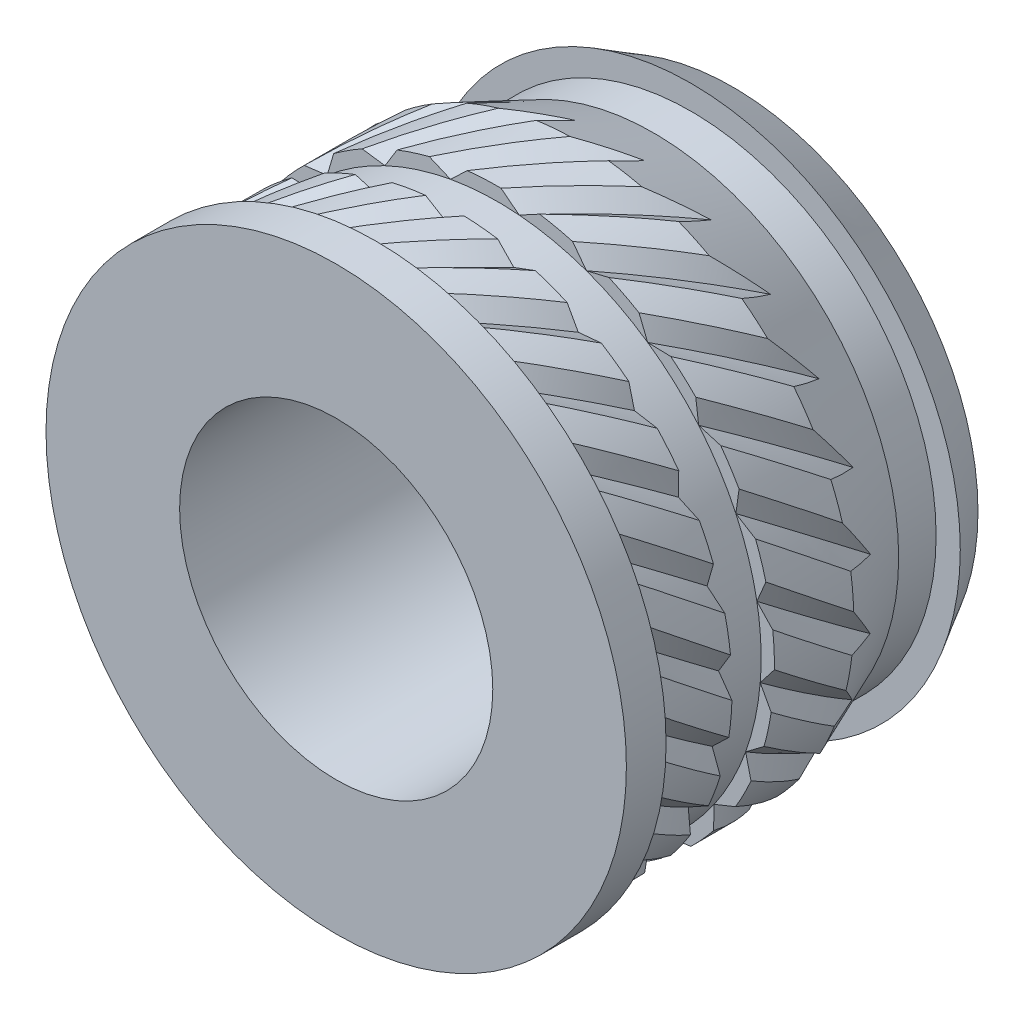
SolidWorks part; units mm, degrees
material "Brass"
ref_plane "Front Plane" through (0, 0, 0) normal (0, 0, 1) x (1, 0, 0)
ref_plane "Top Plane" through (0, 0, 0) normal (0, 1, 0) x (1, 0, 0)
ref_plane "Right Plane" through (0, 0, 0) normal (1, 0, 0) x (0, 0, -1)
sketch "Sketch1" plane through (0, 0, 0) normal (1, 0, 0) x (0, 0, -1)
  line L0 (-1.9, 0) -> (1.9, 0) construction
  line L1 (-1.9, 1.5) -> (-1.9, 2.78)
  line L2 (-1.9, 2.78) -> (-1.52, 2.78)
  line L3 (-1.52, 2.78) -> (-1.52, 2.6525)
  line L4 (-1.52, 2.6525) -> (-0.76, 2.6525)
  line L5 (-0.76, 2.6525) -> (-0.76, 2.525)
  line L6 (-0.76, 2.525) -> (-0.3545, 2.525)
  line L7 (-0.3545, 2.525) -> (-0.3545, 2.6525)
  line L9 (0.4055, 2.6525) -> (1.14, 2.3482)
  line L13 (1.14, 2.3482) -> (1.4986, 2.3482)
  line L14 (1.4986, 2.3482) -> (1.4986, 2.58)
  line L15 (1.4986, 2.58) -> (1.9, 2.3482)
  line L16 (1.9, 2.3482) -> (1.9, 1.5)
  line L17 (-1.9, 2.58) -> (1.9, 2.58) construction
  line L18 (1.9, 0) -> (1.9, 2.58) construction
  line L19 (-1.9, 0) -> (-1.9, 2.78) construction
  line L20 (-0.3545, 2.6525) -> (0.4055, 2.6525)
  line L21 (-1.9, 1.5) -> (1.9, 1.5)
  line L23 (-2.3688, 1.5541) -> (-2.1187, 1.1211) construction
  line L24 (-1.9, -2.58) -> (1.9, -2.58) construction
  line L25 (-2.1187, 1.1211) -> (-1.8687, 1.5541) construction
  line L26 (-1.8687, 1.5541) -> (-2.3688, 1.5541) construction
  line L27 (-2.3375, 1.5) -> (-1.9, 1.5) construction
  line L28 (-2.1187, 1.5541) -> (-2.1187, 1.5) construction
  line L29 (-2.1187, 1.5) -> (-2.1187, 1.1752) construction
  line L30 (-2.1187, 1.1752) -> (-2.1187, 1.1211) construction
  line L31 (-2.15, 1.1752) -> (-2.0875, 1.1752)
  line L32 (-2.3531, 1.5271) -> (-1.8844, 1.5271)
  line L33 (-2.0875, 1.1752) -> (-1.8844, 1.5271)
  line L34 (-2.15, 1.1752) -> (-2.3531, 1.5271)
  line L35 (-1.9, 2.525) -> (1.9, 2.525) construction
  line L36 (-1.9, -2.525) -> (1.9, -2.525) construction
  point P36 (-2.1187, 1.5271)
  dimension "Installed Length" = 3.8
  dimension "Dia A" = 5.56
  dimension "Dia B" = 5.16
  dimension "Thread Dia" = 3
  dimension "D6" = 30
  dimension "D8" = 0.76
  dimension "D4" = 22.5
  dimension "Thread Pitch" = 0.5
  dimension "D2" = 0.0625
  dimension "Max Hole Dia" = 5.05
  dimension "Knurling Length" = 2.66
  dimension "D1" = 4.6965
  dimension "D3" = 0.38
ref_plane "Plane1" through (0, 0, 1.52) normal (0, 0, 1) x (1, 0, 0)
sketch "Sketch2" plane through (0, 0, 1.52) normal (0, 0, 1) x (1, 0, 0)
  line L0 (0, 0) -> (0, 2.6525) construction
  line L1 (-0.1988, 2.6551) -> (0, 2.525)
  line L2 (0.1988, 2.6551) -> (0, 2.525)
  line L3 (-0.185, 2.646) -> (0, 0) construction
  line L4 (0.185, 2.646) -> (0, 0) construction
  line L5 (0, 0) -> (-0.3462, 2.6298) construction
  line L6 (0, 0) -> (0.3462, 2.6298) construction
  line L7 (0, 0) -> (1.8756, 1.8756) construction
  line L8 (0, 0) -> (0, -1.5541) construction
  line L9 (0, 0) -> (0.7771, -1.3459) construction
  circle A0 centre (0, 0) radius 2.525 construction
  circle A1 centre (0, 0) radius 2.6525 construction
  circle A3 centre (0, 0) radius 1.5541
  arc A4 (-0.1988, 2.6551) -> (0.1988, 2.6551) centre (0, 0) cw
  dimension "Knurl Angle" = 8
  dimension "Pattern Angle" = 15
  dimension "Helix Angle" = 45
  dimension "D1" = 30
sketch "Sketch3" plane through (0, 0, 0) normal (1, 0, 0) x (0, 0, -1)
  line L0 (-1.9, 1.5) -> (-1.9, 2.78) construction
  line L1 (-1.9, 2.78) -> (-1.52, 2.78) construction
  line L2 (-1.52, 2.78) -> (-1.52, 2.6525) construction
  line L3 (-1.52, 2.6525) -> (-0.76, 2.6525) construction
  line L4 (-0.76, 2.6525) -> (-0.76, 2.525) construction
  line L5 (-0.76, 2.525) -> (-0.3545, 2.525) construction
  line L6 (-0.3545, 2.525) -> (-0.3545, 2.6525) construction
  line L8 (0.4055, 2.6525) -> (1.14, 2.3482) construction
  line L12 (1.14, 2.3482) -> (1.4986, 2.3482) construction
  line L13 (1.4986, 2.3482) -> (1.4986, 2.58) construction
  line L14 (1.4986, 2.58) -> (1.9, 2.3482) construction
  line L15 (1.9, 2.3482) -> (1.9, 1.5) construction
  line L16 (-1.9, 1.5) -> (1.9, 1.5) construction
  line L17 (-1.9, 1.5) -> (-1.9, 2.78)
  line L18 (-1.9, 2.78) -> (-1.52, 2.78)
  line L19 (-1.52, 2.78) -> (-1.52, 2.6525)
  line L20 (-1.52, 2.6525) -> (-0.76, 2.6525)
  line L21 (-0.76, 2.6525) -> (-0.76, 2.525)
  line L22 (-0.76, 2.525) -> (-0.3545, 2.525)
  line L23 (-0.3545, 2.525) -> (-0.3545, 2.6525)
  line L25 (0.4055, 2.6525) -> (1.14, 2.3482)
  line L29 (1.14, 2.3482) -> (1.4986, 2.3482)
  line L30 (1.4986, 2.3482) -> (1.4986, 2.58)
  line L31 (1.4986, 2.58) -> (1.9, 2.3482)
  line L32 (1.9, 2.3482) -> (1.9, 1.5)
  line L33 (-1.9, 1.5) -> (1.9, 1.5)
  line L34 (-0.3545, 2.6525) -> (0.4055, 2.6525) construction
  line L35 (-0.3545, 2.6525) -> (0.4055, 2.6525)
revolve "Revolve1" add sketch "Sketch3" angle 360 about L0
sketch "Sketch4" plane through (0, 0, 1.52) normal (0, 0, 1) x (1, 0, 0)
  circle A2 centre (0, 0) radius 2.6525 construction
  circle A3 centre (0, 0) radius 2.6525
sketch "Sketch6" [suppressed] plane through (0, 0, 1.9) normal (0, 0, 1) x (1, 0, 0)
  circle A0 centre (0, 0) radius 1.5
curve "Helix/Spiral2" [suppressed] pitch 0.5 height 4.3 turns 8.6
sketch "Sketch7" [suppressed] plane through (0, 0, 0) normal (1, 0, 0) x (0, 0, -1)
  line L0 (-2.15, 1.1752) -> (-2.0875, 1.1752) construction
  line L1 (-2.15, 1.1752) -> (-2.3531, 1.5271) construction
  line L2 (-2.3531, 1.5271) -> (-1.8844, 1.5271) construction
  line L3 (-2.0875, 1.1752) -> (-1.8844, 1.5271) construction
  line L4 (-2.15, 1.1752) -> (-2.0875, 1.1752)
  line L5 (-2.15, 1.1752) -> (-2.3531, 1.5271)
  line L6 (-2.3531, 1.5271) -> (-1.8844, 1.5271)
  line L7 (-2.0875, 1.1752) -> (-1.8844, 1.5271)
sweep "Sweep1" [suppressed] add profiles "Sketch7" path "Helix/Spiral2"
sketch "Sketch8" [suppressed] plane through (0, 0, 1.9) normal (0, 0, 1) x (1, 0, 0)
  circle A0 centre (0, 0) radius 1.5541
extrude "Cut-Extrude1" [suppressed] cut sketch "Sketch8" against normal through all draft 45 and the other way through all
mirror "Mirror1" [suppressed] about plane through (0, 0, 0) normal (0, 0, 1)
curve "Helix/Spiral1" pitch 21.28 height 2.66 radius 2.6525 centre (0, 0, 1.52) axis (0, 0, -1) start towards (0, 1, 0)
sketch "Sketch5" plane through (0, 0, 1.52) normal (0, 0, 1) x (1, 0, 0)
  line L0 (-0.1988, 2.6551) -> (0, 2.525) construction
  line L1 (0.1988, 2.6551) -> (0, 2.525) construction
  line L2 (-0.1988, 2.6551) -> (0, 2.525)
  line L3 (0.1988, 2.6551) -> (0, 2.525)
  arc A2 (0.1988, 2.6551) -> (-0.1988, 2.6551) centre (0, 0) ccw construction
  arc A3 (0.1988, 2.6551) -> (-0.1988, 2.6551) centre (0, 0) ccw
sweep "Cut-Sweep1" cut profiles "Sketch5" path "Helix/Spiral1" align with end faces yes
pattern_circular "CirPattern1" count 24 over 360 about axis through (0, 0, 1.9) along (0, 0, -1) of "Cut-Sweep1"
equation "\"D8@Sketch1\"=\"Installed Length@Sketch1\" * .2"
equation "\"D4@Helix/Spiral1\"=\"Knurling Length@Sketch1\"*(360/\"Helix Angle@Sketch2\")"
equation "\"D3@Helix/Spiral1\"=\"Knurling Length@Sketch1\""
equation "\"D1@CirPattern1\"=\"D3@CirPattern1\"/\"Pattern Angle@Sketch2\""
equation "\"D2@Sketch1\" = \"Thread Pitch@Sketch1\" / 8"
equation "\"D4@Helix/Spiral2\"=\"Thread Pitch@Sketch1\""
equation "\"D3@Helix/Spiral2\" = \"Installed Length@Sketch1\" + \"Thread Pitch@Sketch1\""
equation "\"Knurling Length@Sketch1\"=\"Installed Length@Sketch1\" * .7"
equation "\"D1@Sketch1\"=\"Max Hole Dia@Sketch1\"*.93"
equation "\"D3@Sketch1\"=\"Installed Length@Sketch1\"*.1"
